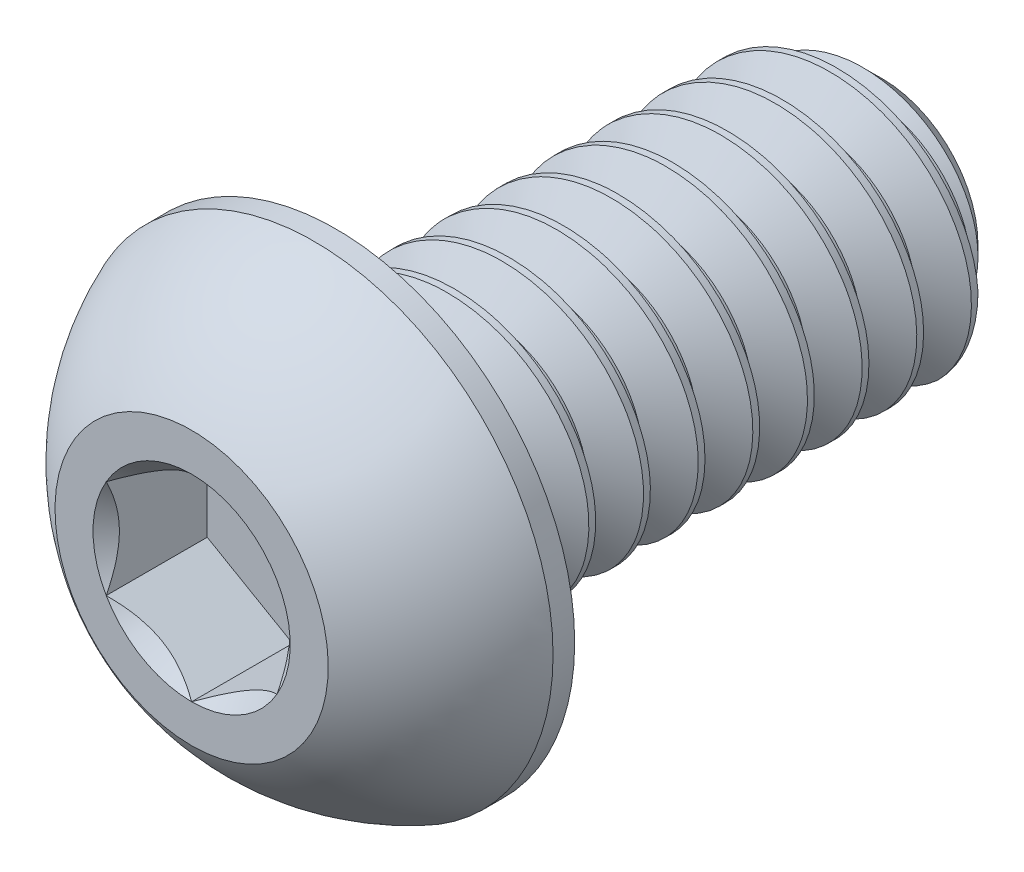
SolidWorks part; units mm, degrees
ref_plane "Front" through (0, 0, 0) normal (0, 0, 1) x (1, 0, 0)
ref_plane "Top" through (0, 0, 0) normal (0, 1, 0) x (1, 0, 0)
ref_plane "Right" through (0, 0, 0) normal (1, 0, 0) x (0, 0, -1)
sketch "Sketch1" plane through (0, 0, 0) normal (1, 0, 0) x (0, 0, -1)
  line L2 (3.3528, 3.175) -> (16.0528, 3.175)
  line L3 (16.0528, 3.175) -> (16.0528, 0)
  line L4 (16.0528, 0) -> (3.3528, 0)
  line L6 (2.8499, 5.5499) -> (3.3528, 5.5499) construction
  line L7 (16.0528, 3.175) -> (16.0528, -3.175) construction
  line L8 (0, 0) -> (3.3528, 0) construction
  line L9 (3.3528, 5.5499) -> (3.3528, -5.5499) construction
  line L11 (3.3528, 3.175) -> (3.3528, 0)
  line L13 (0, 1.9844) -> (0, -1.9844) construction
  line L14 (0, 1.9844) -> (0, 3.175) construction
  arc A3 (0, 3.175) -> (2.8499, 5.5499) centre (5.0603, 0) cw construction
  dimension "D1" = 0.5029
  dimension "Head Ht" = 3.3528
  dimension "Head Dia" = 11.0998
  dimension "Dia" = 6.35
  dimension "Lg" = 12.7
  dimension "Hex" = 3.9688
revolve "Revolve1" add sketch "Sketch1" angle 360 mid plane about L4
sketch "Sketch3" plane through (0, 0, -16.0528) normal (0, 0, -1) x (-1, 0, 0)
  circle A0 centre (0, 0) radius 3.175
curve "Helix/Spiral1" pitch 1.27 height 13.97 radius 3.175 centre (0, 0, -16.0528) axis (0, 0, 1) start towards (0, 1, 0)
sketch "Sketch2" plane through (0, 0, 0) normal (1, 0, 0) x (0, 0, -1)
  line L0 (16.0528, 3.175) -> (17.164, 3.175)
  line L1 (17.164, 3.175) -> (16.6878, 2.3501)
  line L2 (16.6878, 2.3501) -> (16.529, 2.3501)
  line L3 (16.529, 2.3501) -> (16.0528, 3.175)
  line L4 (16.2909, 2.7626) -> (16.9259, 2.7626) construction
  dimension "D1" = 60
  dimension "D2" = 0.1588
  dimension "D3" = 0.635
chamfer "Chamfer1" distance 0.9525 angle 45 1 edges at (0, 3.175, -16.0528)
sweep "Cut-Sweep1" cut profiles "Sketch2" path "Helix/Spiral1"
sketch "Sketch7" plane through (0, 0, 0) normal (1, 0, 0) x (0, 0, -1)
  line L6 (2.8499, 5.5499) -> (3.3528, 5.5499) construction
  line L8 (0, 0) -> (3.3528, 0) construction
  line L11 (3.3528, 5.5499) -> (3.3528, -5.5499) construction
  line L12 (2.8499, 5.5499) -> (3.3528, 5.5499)
  line L13 (0, 0) -> (3.3528, 0)
  line L14 (0, 1.9844) -> (0, -1.9844) construction
  line L15 (3.3528, 5.5499) -> (3.3528, 0)
  line L16 (0, 3.175) -> (0, 0)
  arc A2 (2.8499, 5.5499) -> (0, 3.175) centre (5.0603, 0) ccw construction
  arc A3 (2.8499, 5.5499) -> (0, 3.175) centre (5.0603, 0) ccw
revolve "Revolve2" add sketch "Sketch7" angle 360 mid plane about L13
sketch "Sketch5" plane through (0, 0, 0) normal (0, 0, 1) x (1, 0, 0)
  line L1 (1.9844, -1.1457) -> (1.9844, 1.1457)
  line L2 (1.9844, 1.1457) -> (0, 2.2914)
  line L3 (0, 2.2914) -> (-1.9844, 1.1457)
  line L4 (-1.9844, 1.1457) -> (-1.9844, -1.1457)
  line L5 (-1.9844, -1.1457) -> (0, -2.2914)
  line L6 (0, -2.2914) -> (1.9844, -1.1457)
  circle A0 centre (0, 0) radius 1.9844 construction
extrude "Cut-Extrude2" cut sketch "Sketch5" against normal blind 2.347
sketch "Sketch6" plane through (0, 0, 0) normal (0, 0, 1) x (1, 0, 0)
  circle A0 centre (0, 0) radius 2.2914
extrude "Cut-Extrude3" cut sketch "Sketch6" against normal blind 2.347 draft 45
sketch "Sketch9" [suppressed] plane through (0, 0, -3.3528) normal (0, 0, 1) x (1, 0, 0)
  circle A2 centre (0, 0) radius 3.175
extrude "Boss-Extrude2" [suppressed] add sketch "Sketch9" against normal offset from surface (12.7 mm away) 22.225
sketch "Sketch10" plane through (0, 0, 0) normal (1, 0, 0) x (0, 0, -1)
  line L0 (16.0528, 3.175) -> (16.0528, -3.175) construction
  point P0 (14.1478, -3.175)
  dimension "D1" = 1.905
equation "\"D3@Helix/Spiral1\" = \"Lg@Sketch1\" + \"D4@Helix/Spiral1\""
equation "\"D2@Sketch2\" = \"D4@Helix/Spiral1\" * .125"
equation "\"D3@Sketch2\" = \"D4@Helix/Spiral1\" * .5"
equation "\"D1@Chamfer1\" = \"D4@Helix/Spiral1\" * .75"
equation "\"D1@Cut-Extrude2\" = \"Head Ht@Sketch1\" * .7"
equation "\"D1@Sketch1\" = \"Head Ht@Sketch1\" * .15"
equation "\"D1@Sketch10\" = \"D4@Helix/Spiral1\" * 1.5"
equation "\"D1@Cut-Extrude3\" = \"D1@Cut-Extrude2\""
